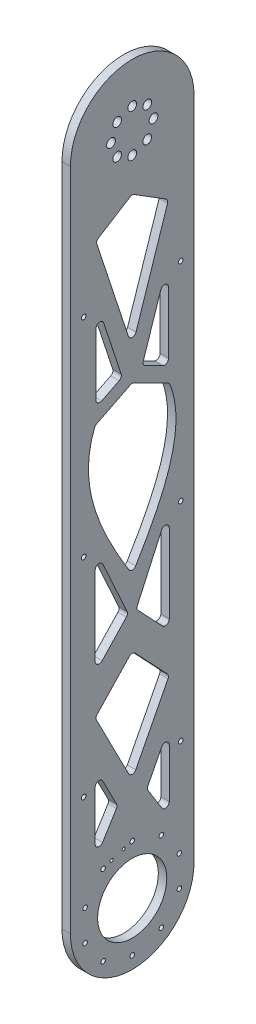
SolidWorks part; units mm, degrees
material "1060 Alloy"
ref_plane "Front Plane" through (0, 0, 0) normal (0, 0, 1) x (1, 0, 0)
ref_plane "Top Plane" through (0, 0, 0) normal (0, 1, 0) x (1, 0, 0)
ref_plane "Right Plane" through (0, 0, 0) normal (1, 0, 0) x (0, 0, -1)
sketch "Sketch1" plane through (0, 0, 0) normal (1, 0, 0) x (0, -1, 0)
  line L0 (0, 0) -> (500, 0) construction
  line L1 (0, 46.5) -> (500, 46.5)
  line L2 (0, -46.5) -> (500, -46.5)
  arc A0 (0, 46.5) -> (0, -46.5) centre (0, 0) ccw
  arc A1 (500, -46.5) -> (500, 46.5) centre (500, 0) ccw
  circle A2 centre (0, 0) radius 16 construction
  circle A3 centre (-16, 0) radius 3.3
  circle A4 centre (-11.3137, 11.3137) radius 3.3
  circle A5 centre (0, 16) radius 3.3
  circle A6 centre (11.3137, 11.3137) radius 3.3
  circle A7 centre (16, 0) radius 3.3
  circle A8 centre (11.3137, -11.3137) radius 3.3
  circle A27 centre (500, 0) radius 37.25 construction
  circle A28 centre (537.25, 0) radius 1.7
  circle A29 centre (500, 0) radius 37.25 construction
  circle A30 centre (537.25, 0) radius 1.7
  circle A31 centre (530.1359, -21.895) radius 1.7
  circle A32 centre (511.5109, -35.4269) radius 1.7
  circle A33 centre (488.4891, -35.4269) radius 1.7
  circle A34 centre (469.8641, -21.895) radius 1.7
  circle A35 centre (462.75, 0) radius 1.7
  circle A36 centre (469.8641, 21.895) radius 1.7
  circle A37 centre (488.4891, 35.4269) radius 1.7
  circle A38 centre (511.5109, 35.4269) radius 1.7
  circle A39 centre (530.1359, 21.895) radius 1.7
  circle A40 centre (500, 0) radius 26
  circle A41 centre (0, -16) radius 3.3
  circle A42 centre (-11.3137, -11.3137) radius 3.3
  point P3 (250, 0)
  point P25 (0, 0)
  point P52 (500, 0)
  point P61 (500, 0)
  dimension "D3" = 32
  dimension "D4" = 6.6
  dimension "D2" = 74.5
  dimension "D7" = 3.4
  dimension "D8" = 3.4
  dimension "D10" = 52
  dimension "D6" = 46.5
  dimension "D1" = 500
  dimension "D5" = 8
  dimension "D9" = 10
extrude "Boss-Extrude1" add sketch "Sketch1" along normal blind 6.35 contours L2 A1 L1 A0 A40 A39 A38 A37 A36 A35 A34 A33 A32 A31 A28 A8 A7 A6 A5 A4 A3 region at (0, -240.4496, 0)
ref_axis "Axis1" through (6.35, -500, 0) along (-1, 0, 0)
sketch "Sketch3" plane through (6.35, 0, 0) normal (1, 0, 0) x (0, 0, -1)
  line L0 (0, -500) -> (0, 0) construction
  line L1 (0, -422.848) -> (27.8582, -368.6328)
  line L2 (0, -422.848) -> (-27.8582, -368.6328)
  line L3 (-27.8582, -368.6328) -> (0, -339.1393)
  line L4 (0, -339.1393) -> (27.8582, -368.6328)
  line L5 (0, -41.3687) -> (-27.3129, -58.4352)
  line L6 (-27.3129, -58.4352) -> (0, -141.249)
  line L7 (0, -141.249) -> (27.3129, -58.4352)
  line L8 (27.3129, -58.4352) -> (0, -41.3687)
  line L9 (3, -313.1891) -> (27.8582, -339.5065)
  line L10 (27.8582, -339.5065) -> (27.8582, -258.646)
  line L11 (27.8582, -258.646) -> (3, -313.1891)
  line L12 (-27.8582, -339.5065) -> (-27.8582, -258.646)
  line L13 (-3, -313.1891) -> (-27.8582, -339.5065)
  line L14 (-27.8582, -258.646) -> (-3, -313.1891)
  line L15 (-27.8582, -401.4529) -> (-11, -434.2608)
  line L16 (-11, -434.2608) -> (-27.8582, -461.4818)
  line L17 (-27.8582, -461.4818) -> (-27.8582, -401.4529)
  line L18 (11, -434.2608) -> (27.8582, -461.4818)
  line L19 (27.8582, -401.4529) -> (11, -434.2608)
  line L20 (27.8582, -461.4818) -> (27.8582, -401.4529)
  line L21 (0, -164.2489) -> (-27.8582, -178.2005)
  line L22 (0, -164.2489) -> (27.8582, -178.2005)
  line L23 (7.5, -156.821) -> (27.3129, -96.7475)
  line L24 (27.3129, -96.7475) -> (27.3129, -166.7434)
  line L25 (27.3129, -166.7434) -> (7.5, -156.821)
  line L26 (-27.3129, -96.7475) -> (-27.3129, -166.7434)
  line L27 (-7.5, -156.821) -> (-27.3129, -96.7475)
  line L28 (-27.3129, -166.7434) -> (-7.5, -156.821)
  spline S0 degree 3 poles (-27.8582, -178.2005) (-43.7791, -216.0933) (-18.6166, -258.2761) (0, -289.085) knots 0 0 0 0 1 1 1 1
  spline S1 degree 3 poles (27.8582, -178.2005) (43.7791, -216.0933) (18.6166, -258.2761) (0, -289.085) knots 0 0 0 0 1 1 1 1
  dimension "D1" = 15
  dimension "D2" = 20
  dimension "D3" = 12
  dimension "D4" = 10
  dimension "D5" = 6
  dimension "D6" = 15
  dimension "D7" = 22
extrude "Cut-Extrude1" cut sketch "Sketch3" against normal through all
fillet "Fillet1" radius 3 30 edges at (3.175, -58.4352, -27.3129) (3.175, -41.3687, 0) (3.175, -58.4352, 27.3129) (3.175, -141.249, 0) (3.175, -289.085, 0) (3.175, -164.2489, 0) (3.175, -401.4529, 27.8582) (3.175, -434.2608, 11) (3.175, -461.4818, 27.8582) (3.175, -461.4818, -27.8582) (3.175, -434.2608, -11) (3.175, -401.4529, -27.8582) (3.175, -368.6328, -27.8582) (3.175, -339.1393, 0) (3.175, -368.6328, 27.8582) (3.175, -422.848, 0) (3.175, -313.1891, 3) (3.175, -339.5065, 27.8582) (3.175, -258.646, 27.8582) (3.175, -178.2005, -27.8582) (3.175, -178.2005, 27.8582) (3.175, -339.5065, -27.8582) (3.175, -313.1891, -3) (3.175, -258.646, -27.8582) (3.175, -96.7475, 27.3129) (3.175, -166.7434, 27.3129) (3.175, -156.821, 7.5) (3.175, -166.7434, -27.3129) (3.175, -156.821, -7.5) (3.175, -96.7475, -27.3129)
sketch "Sketch4" plane through (6.35, 0, 0) normal (1, 0, 0) x (0, 0, -1)
  line L0 (0, 46.5) -> (-113.1579, 46.5) construction
  line L1 (-46.5, 0) -> (-46.5, -500) construction
  line L2 (-46.5, -100) -> (46.5, -100) construction
  line L3 (46.5, 0) -> (46.5, -500) construction
  line L4 (-46.5, -106.35) -> (46.5, -106.35) construction
  line L5 (-36.5, -100) -> (-36.5, -106.35) construction
  line L6 (0, 0) -> (0, -106.35) construction
  line L7 (0, -106.35) -> (0, -256.35) construction
  line L8 (0, -256.35) -> (46.5, -256.35) construction
  line L9 (46.5, -262.7) -> (-46.5, -262.7) construction
  line L10 (0, -181.35) -> (46.5, -181.35) construction
  line L11 (0, -262.7) -> (0, -412.7) construction
  line L12 (0, -412.7) -> (46.5, -412.7) construction
  line L13 (0, -337.7) -> (46.5, -337.7) construction
  arc A1 (46.5, 0) -> (-46.5, 0) centre (0, 0) ccw construction
  circle A2 centre (-36.5, -103.175) radius 1.75
  circle A3 centre (36.5, -103.175) radius 1.75
  circle A4 centre (-36.5, -259.525) radius 1.75
  circle A5 centre (36.5, -259.525) radius 1.75
  circle A6 centre (-36.5, -415.875) radius 1.75
  circle A7 centre (36.5, -415.875) radius 1.75
  point P17 (-36.5, -103.175)
  dimension "D1" = 3.5
  dimension "D2" = 6.35
  dimension "D3" = 10
  dimension "D4" = 146.5
  dimension "D5" = 150
  dimension "D6" = 6.35
  dimension "D7" = 81.35
  dimension "D8" = 150
  dimension "D9" = 81.35
extrude "Cut-Extrude2" cut sketch "Sketch4" against normal through all
sketch "Sketch5" plane through (6.35, 0, 0) normal (1, 0, 0) x (0, 0, -1)
  line L0 (-6.4835, -464.6746) -> (-15.5185, -467.6102) construction
  line L1 (-7.2252, -475.0096) -> (7.4545, -470.2399) construction
  line L2 (-21.895, -469.8641) -> (0, -462.75) construction
  line L3 (-10.9475, -466.3071) -> (0, -500) construction
  circle A0 centre (-6.4835, -464.6746) radius 1.2
  circle A1 centre (-15.5185, -467.6102) radius 1.2
  circle A2 centre (0, -500) radius 26 construction
  circle A3 centre (0, -500) radius 26 construction
  circle A4 centre (0, -462.75) radius 1.7 construction
  circle A5 centre (-21.895, -469.8641) radius 1.7 construction
  circle A6 centre (0, -462.75) radius 1.7 construction
  circle A7 centre (-21.895, -469.8641) radius 1.7 construction
  point P16 (-11.001, -466.1424)
  dimension "D1" = 2.4
  dimension "D2" = 9.5
  dimension "D3" = 9.6
extrude "Cut-Extrude4" cut sketch "Sketch5" against normal through all
equation "\"L1L\"=500"
equation "\"D1@Sketch1\"=\"L1L\""
equation "\"L1Thick\"=6.35"
equation "\"D1@Boss-Extrude1\"=\"L1Thick\""
equation "\"Harm-Drive-Outer\"=74.5"
equation "\"D2@Sketch1\"=\"Harm-Drive-Outer\""
